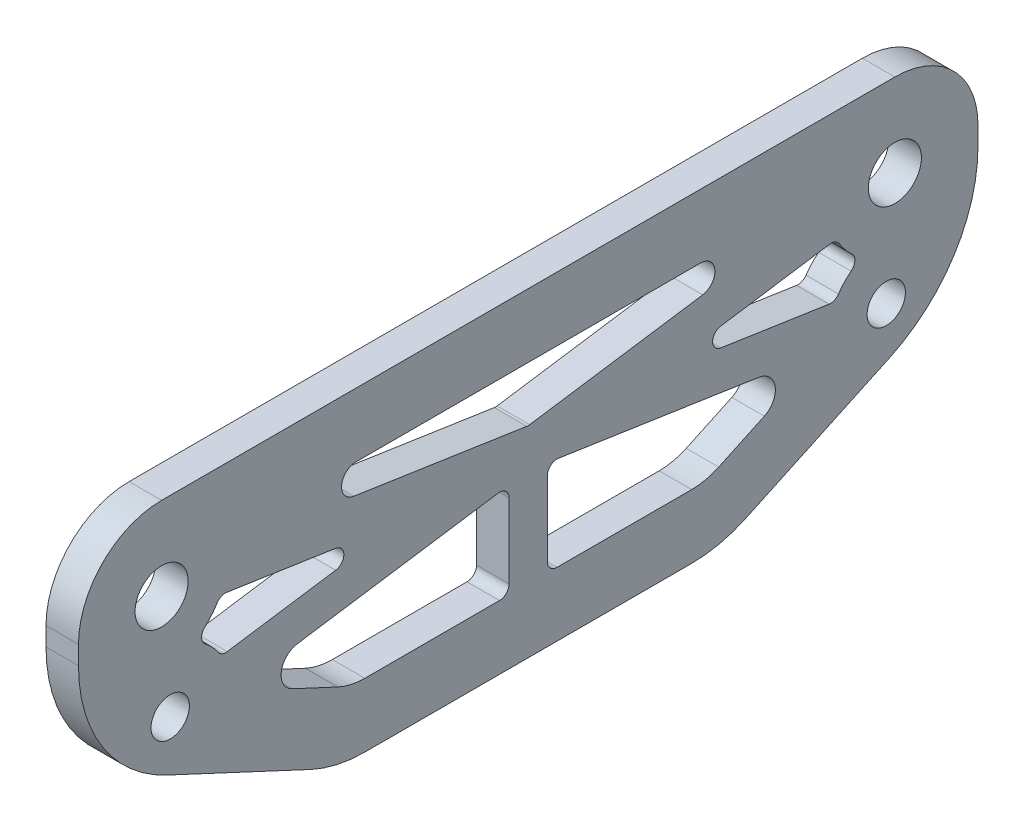
SolidWorks part; units mm, degrees
ref_plane "Front Plane" through (0, 0, 0) normal (0, 0, 1) x (1, 0, 0)
ref_plane "Top Plane" through (0, 0, 0) normal (0, 1, 0) x (1, 0, 0)
ref_plane "Right Plane" through (0, 0, 0) normal (1, 0, 0) x (0, 0, -1)
sketch "Sketch1" plane through (0, 0, 0) normal (1, 0, 0) x (0, 0, -1)
  line L0 (15, 12.5) -> (28.675, 12.5)
  line L1 (-15, -12.5) -> (15, -12.5)
  line L3 (-15, 12.5) -> (15, 12.5)
  line L5 (-15, -12.5) -> (15, 12.5) construction
  line L6 (-15, 12.5) -> (15, -12.5) construction
  line L8 (0, 12.5) -> (0, -12.5) construction
  line L10 (-15, 12.5) -> (-28.675, 12.5)
  line L11 (23.175, 170.0303) -> (23.175, -57.3697) construction
  line L13 (35.175, 6) -> (35.175, 4.5526)
  line L14 (28.2464, -6.3231) -> (15, -12.5)
  line L16 (-35.175, 6) -> (-35.175, 4.5526)
  line L17 (-28.2464, -6.3231) -> (-15, -12.5)
  arc A0 (28.675, 12.5) -> (35.175, 6) centre (28.675, 6) cw
  circle A1 centre (28.675, 6) radius 5.5 construction
  circle A2 centre (-28.675, 6) radius 5.5 construction
  arc A3 (-28.675, 12.5) -> (-35.175, 6) centre (-28.675, 6) ccw
  arc A4 (35.175, 4.5526) -> (28.2464, -6.3231) centre (23.175, 4.5526) cw
  circle A5 centre (28.675, 6) radius 2.075
  arc A6 (-35.175, 4.5526) -> (-28.2464, -6.3231) centre (-23.175, 4.5526) ccw
  circle A9 centre (-28.675, 6) radius 2.075
  circle A11 centre (28, -2.5) radius 1.5
  circle A12 centre (-28, -2.5) radius 1.5
  point P0 (0, 0)
  point P28 (0, 0)
  dimension "D1" = 11
  dimension "D2" = 1
  dimension "D3" = 4.15
  dimension "D4" = 3
  dimension "D6" = 25
  dimension "D8" = 12
  dimension "D5" = 25
  dimension "D7" = 30
  dimension "D9" = 28
  dimension "D10" = 2.5
extrude "Boss-Extrude1" add sketch "Sketch1" along normal blind 2.54
fillet "Fillet1" radius 10 2 edges at (1.27, -12.5, -15) (1.27, -12.5, 15)
sketch "Sketch2" plane through (0, 0, 0) normal (1, 0, 0) x (0, 0, -1)
  line L0 (-28.675, 6) -> (28, -2.5) construction
  line L10 (-28.675, -2.6012) -> (28.675, 6)
  line L11 (-28.675, 6) -> (28, -2.5)
  line L12 (-28.8975, 4.5166) -> (27.7775, -3.9834)
  line L13 (-28.4525, 7.4834) -> (28.2225, -1.0166)
  line L14 (-28.8975, 4.5166) -> (-28.4525, 7.4834)
  line L15 (27.7775, -3.9834) -> (28.2225, -1.0166)
  line L16 (-12.7831, -7.5) -> (12.7831, -7.5)
  line L17 (14.8961, -7.0315) -> (26.1333, -1.7916)
  line L18 (30.175, 4.5526) -> (30.175, 6)
  line L19 (28.675, 7.5) -> (-28.675, 7.5)
  line L20 (-30.175, 6) -> (-30.175, 4.5526)
  line L21 (-26.1333, -1.7916) -> (-14.8961, -7.0315)
  line L22 (-12.7831, -7.5) -> (12.7831, -7.5)
  line L23 (14.8961, -7.0315) -> (26.1333, -1.7916)
  line L24 (30.175, 4.5526) -> (30.175, 6)
  line L25 (28.675, 7.5) -> (-28.675, 7.5)
  line L26 (-30.175, 6) -> (-30.175, 4.5526)
  line L27 (-26.1333, -1.7916) -> (-14.8961, -7.0315)
  line L28 (-28.4525, -4.0846) -> (28.8975, 4.5166)
  line L29 (-28.8975, -1.1178) -> (28.4525, 7.4834)
  line L30 (-28.4525, -4.0846) -> (-28.8975, -1.1178)
  line L31 (28.8975, 4.5166) -> (28.4525, 7.4834)
  line L32 (0, -7.5) -> (0, 7.5) construction
  line L33 (0, 1.6994) -> (0, -7.5)
  line L34 (-1.5, 1.6994) -> (-1.5, -7.5)
  line L35 (1.5, 1.6994) -> (1.5, -7.5)
  line L36 (-1.5, 1.6994) -> (1.5, 1.6994)
  line L37 (-1.5, -7.5) -> (1.5, -7.5)
  arc A0 (-18.0527, -2.5249) -> (-18.4641, -5.3678) centre (-17.8302, -4.0083) ccw
  arc A1 (18.0527, -2.5249) -> (18.4641, -5.3678) centre (17.8302, -4.0083) cw
  circle A2 centre (-28, -2.5) radius 4.5
  circle A3 centre (-28, -2.5) radius 4.5
  circle A5 centre (28, -2.5) radius 4.5
  circle A6 centre (28, -2.5) radius 4.5
  circle A11 centre (-28.675, 6) radius 5.075
  arc A12 (12.7831, -7.5) -> (14.8961, -7.0315) centre (12.7831, -2.5) ccw
  arc A13 (26.1333, -1.7916) -> (30.175, 4.5526) centre (23.175, 4.5526) ccw
  arc A14 (30.175, 6) -> (28.675, 7.5) centre (28.675, 6) ccw
  arc A15 (-28.675, 7.5) -> (-30.175, 6) centre (-28.675, 6) ccw
  arc A16 (-30.175, 4.5526) -> (-26.1333, -1.7916) centre (-23.175, 4.5526) ccw
  arc A17 (-14.8961, -7.0315) -> (-12.7831, -7.5) centre (-12.7831, -2.5) ccw
  arc A18 (12.7831, -7.5) -> (14.8961, -7.0315) centre (12.7831, -2.5) ccw
  arc A19 (26.1333, -1.7916) -> (30.175, 4.5526) centre (23.175, 4.5526) ccw
  arc A20 (30.175, 6) -> (28.675, 7.5) centre (28.675, 6) ccw
  arc A21 (-28.675, 7.5) -> (-30.175, 6) centre (-28.675, 6) ccw
  arc A22 (-30.175, 4.5526) -> (-26.1333, -1.7916) centre (-23.175, 4.5526) ccw
  arc A23 (-14.8961, -7.0315) -> (-12.7831, -7.5) centre (-12.7831, -2.5) ccw
  circle A24 centre (-28.675, 6) radius 5.075
  circle A26 centre (28.675, 6) radius 5.075
  circle A27 centre (28.675, 6) radius 5.075
  arc A32 (13.477, 7.5) -> (13.6439, 5.2624) centre (13.477, 6.375) cw
  arc A33 (-13.477, 7.5) -> (-13.6439, 5.2624) centre (-13.477, 6.375) ccw
  dimension "D11" = 3
  dimension "D12" = 1.125
  dimension "D2" = 1.5
  dimension "D1" = 5
  dimension "D3" = 3
  dimension "D4" = 3
  dimension "D6" = 1.5
  dimension "D7" = 1.5
  dimension "D8" = 1.5
  dimension "D9" = 1.5
  dimension "D13" = 1.5
  dimension "D14" = 1.5
  dimension "D15" = 3
extrude "Cut-Extrude2" cut sketch "Sketch2" along normal through all contours A24 A3 L29 L12 | A27 L28 L13 A6 | L25 A33 L13 L29 A32 | A1 L12 L35 L22 | L28 A0 L22 L34 region at (0, 1.7005, 19.9688) region at (0, -4.2389, 9.1911) region at (0, 5.8357, 0) region at (0, -4.2389, -9.1911) region at (0, 1.7005, -19.9688)
fillet "Fillet2" radius 0.75 13 edges at (1.27, -7.5, -1.5) (1.27, 3.7975, -24.1028) (1.27, 1.6994, -10.1133) (1.27, 3.7975, 24.1028) (1.27, 3.2162, 0) (1.27, -0.0424, -1.5) (1.27, -7.5, 1.5) (1.27, -0.0424, 1.5) (1.27, 1.6994, 10.1133) (1.27, -0.3873, -24.0268) (1.27, 1.6002, -26.1457) (1.27, -0.3873, 24.0268) (1.27, 1.6002, 26.1457)
